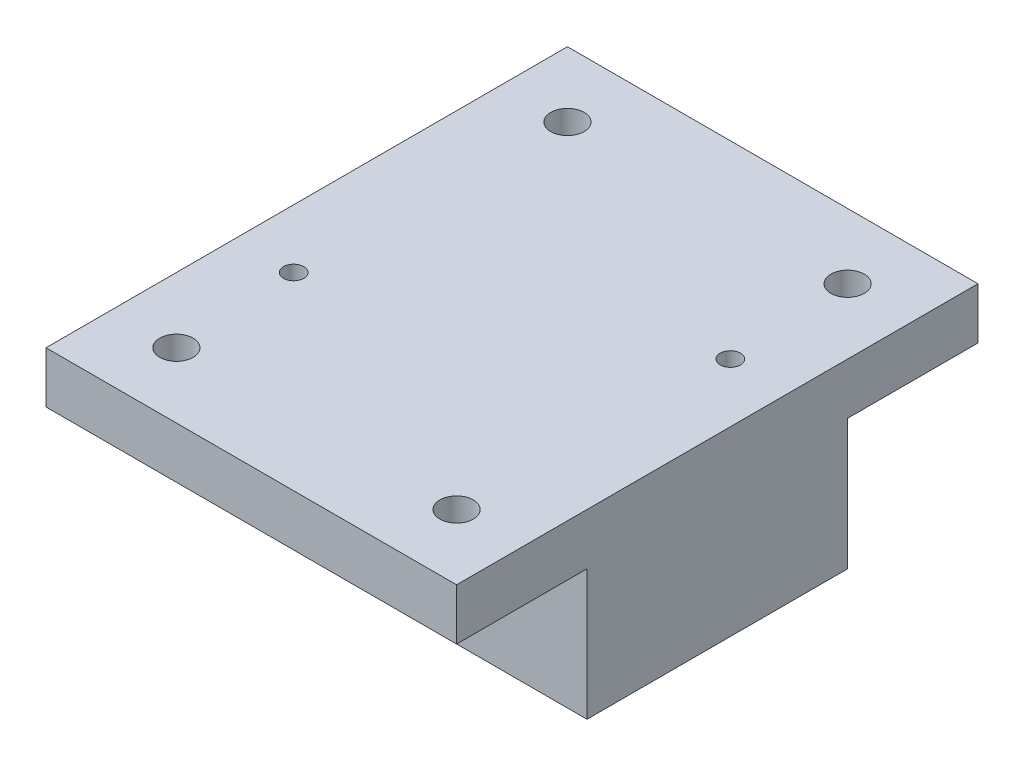
SolidWorks part; units mm, degrees
material "PETG"
ref_plane "Front Plane" through (0, 0, 0) normal (0, 0, 1) x (1, 0, 0)
ref_plane "Top Plane" through (0, 0, 0) normal (0, 1, 0) x (1, 0, 0)
ref_plane "Right Plane" through (0, 0, 0) normal (1, 0, 0) x (0, 0, -1)
sketch "Sketch1" plane through (0, 0, 0) normal (0, 1, 0) x (1, 0, 0)
  line L0 (-27.295, 38.095) -> (-27.295, 50.8) construction
  line L1 (-40, -25.39) -> (40, -25.39)
  line L2 (-40, -25.39) -> (-40, 25.39)
  line L3 (-40, 25.39) -> (40, 25.39)
  line L4 (40, -25.39) -> (40, 25.39)
  line L5 (-40, 50.8) -> (40, 50.8)
  line L6 (-40, 50.8) -> (-40, -50.8)
  line L7 (-40, -50.8) -> (40, -50.8)
  line L8 (40, 50.8) -> (40, -50.8)
  line L9 (-27.295, 38.095) -> (-40, 38.095) construction
  line L10 (-27.295, 38.095) -> (-27.295, 25.39) construction
  line L11 (27.295, 38.095) -> (40, 38.095) construction
  line L13 (-27.295, -38.095) -> (-27.295, -25.39) construction
  circle A0 centre (-27.295, 38.095) radius 3.25
  circle A1 centre (27.295, 38.095) radius 3.25
  circle A2 centre (-27.295, -38.095) radius 3.25
  circle A3 centre (27.295, -38.095) radius 3.25
  point P4 (-40, 0)
  point P5 (0, 25.39)
  dimension "D4" = 6.5
  dimension "D1" = 50.78
  dimension "D2" = 80
  dimension "D3" = 101.6
extrude "Boss-Extrude1" add sketch "Sketch1" along normal blind 10 contours L1 L4 L3 L2 | L8 L1 L6 L7 | L8 L5 L6 L3 region at (0, 0, 0) region at (0, 0, 38.095) region at (0, 0, -38.095)
extrude "Boss-Extrude2" add sketch "Sketch1<3>" against normal blind 25.4 contours L1 L4 L3 L2 region at (0, 0, 0)
sketch "Sketch1<3>" plane through (0, 0, 0) normal (0, 1, 0) x (1, 0, 0) same geometry as "Sketch1"
sketch "Sketch2" plane through (0, 10, 0) normal (0, 1, 0) x (1, 0, 0)
  line L0 (-40, 0) -> (40, 0) construction
  line L1 (-40, -50.8) -> (-40, 50.8) construction
  line L2 (40, -50.8) -> (40, 50.8) construction
  line L3 (0, 50.8) -> (0, -50.8) construction
  line L4 (-40, 50.8) -> (40, 50.8) construction
  line L5 (-40, -50.8) -> (40, -50.8) construction
  line L6 (-28.575, -13.97) -> (-28.575, 0) construction
  line L7 (-28.575, -13.97) -> (0, -13.97) construction
  line L8 (28.575, 0) -> (28.575, 13.97) construction
  line L9 (28.575, 13.97) -> (0, 13.97) construction
  circle A0 centre (-28.575, -13.97) radius 1.985
  circle A1 centre (28.575, 13.97) radius 1.985
  dimension "D2" = 3.97
  dimension "D1" = 13.97
  dimension "D3" = 28.575
extrude "Cut-Extrude1" cut sketch "Sketch2" against normal through all
equation "\"tol_dia_id_intfc\" = 0.0200mm ' For hole diameters - Interference fit"
equation "\"tol_dia_id_slip\"  = 0.0300mm ' For hole diameters - Slip fit"
equation "\"tol_dia_id_clear\" = 0.0500mm ' For hole diameters - Clearance fit"
equation "\"tol_dia_od_intfc\" = 0.0200mm ' For shaft diameters - Interference fit"
equation "\"tol_dia_od_slip\"  = 0.0300mm ' For shaft diameters - Slip fit"
equation "\"tol_dia_od_clear\" = 0.0500mm ' For shaft diameters - Clearance fit"
equation "\"tol_general_intfc\"= 0.0030mm ' For general parts (Horiz) - Interference fit"
equation "\"tol_general_slip\" = 0.0050mm ' For general parts (Horiz) - Slip fit"
equation "\"tol_general_clear\"= 0.0100mm ' For general parts (Horiz) - Clearance fit"
equation "\"tol_layer_intfc\"  = 0.0030mm ' For all parts (Vert) - Interference fit"
equation "\"tol_layer_slip\"   = 0.0050mm ' For all parts (Vert) - Slip fit"
equation "\"tol_layer_clear\"  = 0.0100mm ' For all parts (Vert) - Clearance fit"
equation "\"tol_corner_rad\"   = 0.100mm ' For corners that fit into other parts"
equation "\"D1@Sketch1\"= 50.80mm - \"tol_general_clear\" * 2"
equation "\"D2@Sketch2\"=3.95+\"tol_dia_id_intfc\""
